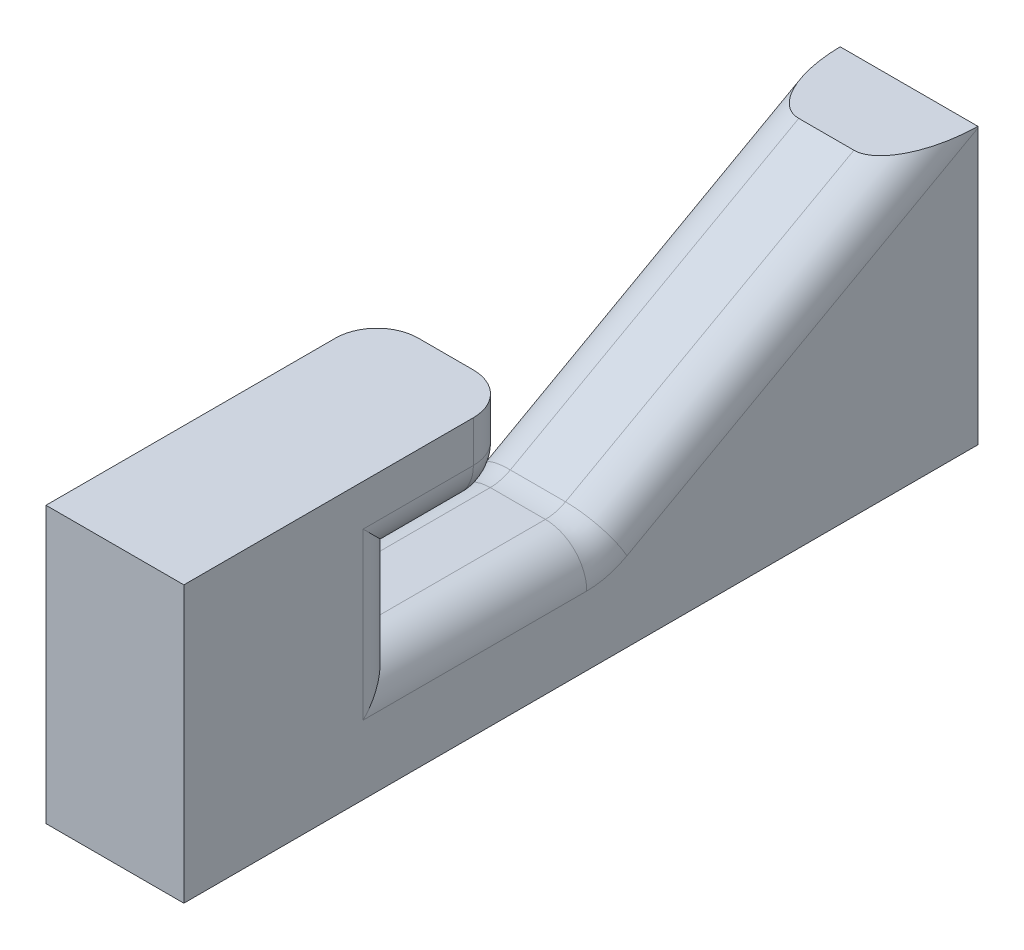
SolidWorks part; units mm, degrees
ref_plane "Front Plane" through (0, 0, 0) normal (1, 0, 0) x (0, 1, 0)
ref_plane "Top Plane" through (0, 0, 0) normal (0, 0, 1) x (0, 1, 0)
ref_plane "Right Plane" through (0, 0, 0) normal (0, 1, 0) x (-1, 0, 0)
sketch "Sketch2" plane through (0, 0, 0) normal (1, 0, 0) x (0, 1, 0)
  line L1 (0, 0) -> (10, 0)
  line L2 (0, 0) -> (0, 28.8)
  line L3 (0, 28.8) -> (10, 28.8)
  line L4 (10, 0) -> (10, 28.8)
  dimension "D1" = 28.8
  dimension "D2" = 10
extrude "Boss-Extrude1" add sketch "Sketch2" along normal blind 5
sketch "Sketch3" plane through (5, 0, 0) normal (1, 0, 0) x (0, 1, 0)
  line L0 (4, 16.8) -> (4, 13.8)
  line L1 (10, 28.8) -> (7, 28.8)
  line L2 (10, 28.8) -> (10, 16.8)
  line L3 (10, 16.8) -> (7, 16.8)
  line L4 (7, 28.8) -> (7, 16.8)
  line L5 (7, 16.8) -> (4, 16.8)
  line L6 (7, 16.8) -> (7, 20.8)
  line L7 (7, 20.8) -> (4, 20.8)
  line L8 (4, 16.8) -> (4, 20.8)
  line L10 (4, 13.8) -> (10, 3)
  line L11 (10, 0) -> (10, 28.8) construction
  line L12 (0, 0) -> (10, 0) construction
  line L13 (10, 3) -> (10, 16.8)
  line M12 (10, 0) -> (10, 28.8)
  dimension "D1" = 12
  dimension "D2" = 3
  dimension "D3" = 3
  dimension "D4" = 4
  dimension "D5" = 3
  dimension "D6" = 3
extrude "Cut-Extrude1" cut sketch "Sketch3" against normal through all contours L8 L5 L4 L7 | L0 L10 L3 L5 M12 region at (5, 7.6429, 12.0214) region at (5, 5.5, 18.8)
fillet "Fillet2" radius 1.5 12 edges at (2.5, 7, 16.8) (5, 7, 18.8) (5, 4, 17.3) (5, 5.5, 20.8) (0, 4, 17.3) (0, 5.5, 20.8) (0, 7, 18.8) (0, 7, 8.4) (5, 7, 8.4) (2.5, 4, 13.8) (0, 8.5, 16.8) (5, 8.5, 16.8)
equation "\"whitekey_cutout_length\"= 101.5"
equation "\"wall_thickness\"=10"
equation "\"base_mount_height\"=40"
equation "\"base_rear_length\"=80"
equation "\"D1@Sketch2\"=\"base_mount_height\"-11-0.2"
equation "\"key_mount_recess_length\"=50"
equation "\"key_mount_recess_height\"=12.5"
equation "\"key_mount_recess_depth\"=1.5"
equation "\"guide_brace_height\"=20"
equation "\"guide_brace_thickness\"=2"
equation "\"dowel_recess_depth\"=10"
equation "\"dowel_recess_offset\"=3.25"
equation "\"base_front_length\"=111.5"
equation "\"screw_hole_wall_offset\"=7.25"
equation "\"screw_hole_edge_inset\"=\"dowel_recess_depth\"/2"
equation "\"screw_hole_diameter\"=3.8"
equation "\"screw_head_hole_diameter\"=6.7"
equation "\"screw_nut_hole_side_len\"=3.5"
equation "\"screw_shaft_diameter\"=3.5"
equation "\"switch_board_width\"=30"
equation "\"heatset_insert_hole_diameter\"=4.8"
equation "\"heatset_insert_hole_depth\"=3.8"
